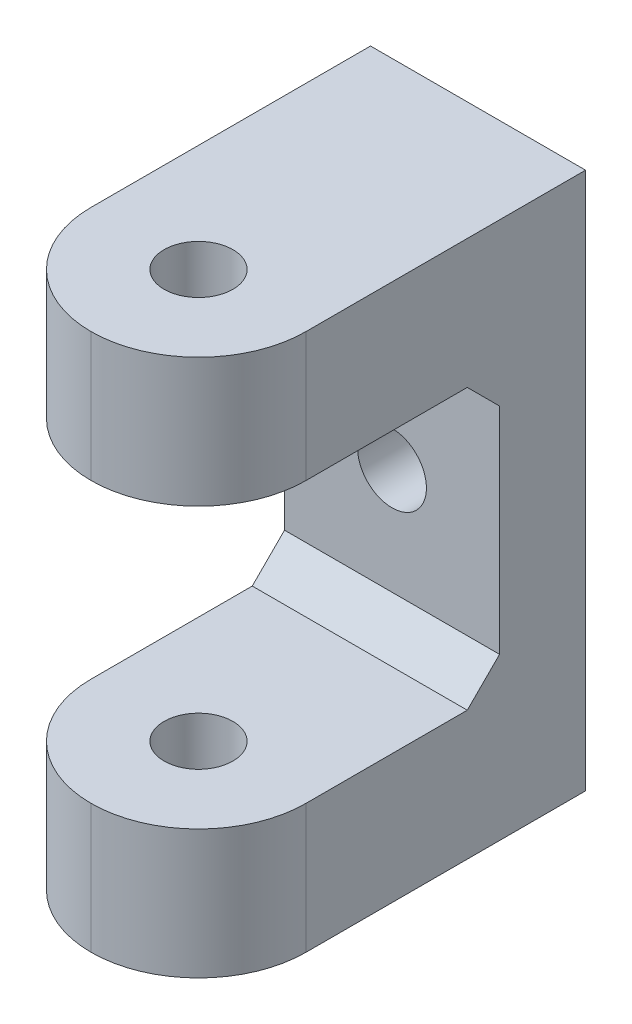
SolidWorks part; units mm, degrees
material "PET"
ref_plane "Front Plane" through (0, 0, 0) normal (0, 0, 1) x (1, 0, 0)
ref_plane "Top Plane" through (0, 0, 0) normal (0, 1, 0) x (1, 0, 0)
ref_plane "Right Plane" through (0, 0, 0) normal (1, 0, 0) x (0, 0, -1)
sketch "Sketch1" plane through (0, 0, 0) normal (0, 0, 1) x (1, 0, 0)
  line L1 (0, 0) -> (10, 0)
  line L2 (0, 0) -> (0, 6)
  line L3 (0, 6) -> (10, 6)
  line L4 (10, 0) -> (10, 6)
  line L5 (0, 19) -> (10, 19)
  line L6 (0, 19) -> (0, 25)
  line L7 (0, 25) -> (10, 25)
  line L8 (10, 19) -> (10, 25)
  dimension "D1" = 6
  dimension "D2" = 25
  dimension "D3" = 10
extrude "Boss-Extrude1" add sketch "Sketch1" along normal blind 15
fillet "Fillet1" radius 5 2 edges at (10, 22, 15) (0, 22, 15)
fillet "Fillet2" radius 5 2 edges at (10, 3, 15) (0, 3, 15)
sketch "Sketch2" plane through (0, 0, 0) normal (0, 0, -1) x (-1, 0, 0)
  line L1 (-10, 25) -> (0, 25)
  line L2 (-10, 25) -> (-10, 0)
  line L3 (-10, 0) -> (0, 0)
  line L4 (0, 25) -> (0, 0)
extrude "Boss-Extrude2" add sketch "Sketch2" along normal blind 3 and the other way blind 1
sketch "Sketch3" plane through (0, 25, 0) normal (0, 1, 0) x (1, 0, 0)
  circle A0 centre (5, -10) radius 1.6
  dimension "D1" = 3.2
extrude "Cut-Extrude1" cut sketch "Sketch3" against normal through all
sketch "Sketch4" plane through (0, 0, -3) normal (0, 0, -1) x (-1, 0, 0)
  circle A0 centre (-5, 12.5) radius 1.6
  dimension "D1" = 3.2
extrude "Cut-Extrude2" cut sketch "Sketch4" against normal up to next
chamfer "Chamfer1" distance 1.5 angle 45 2 edges at (5, 6, 1) (5, 19, 1)
